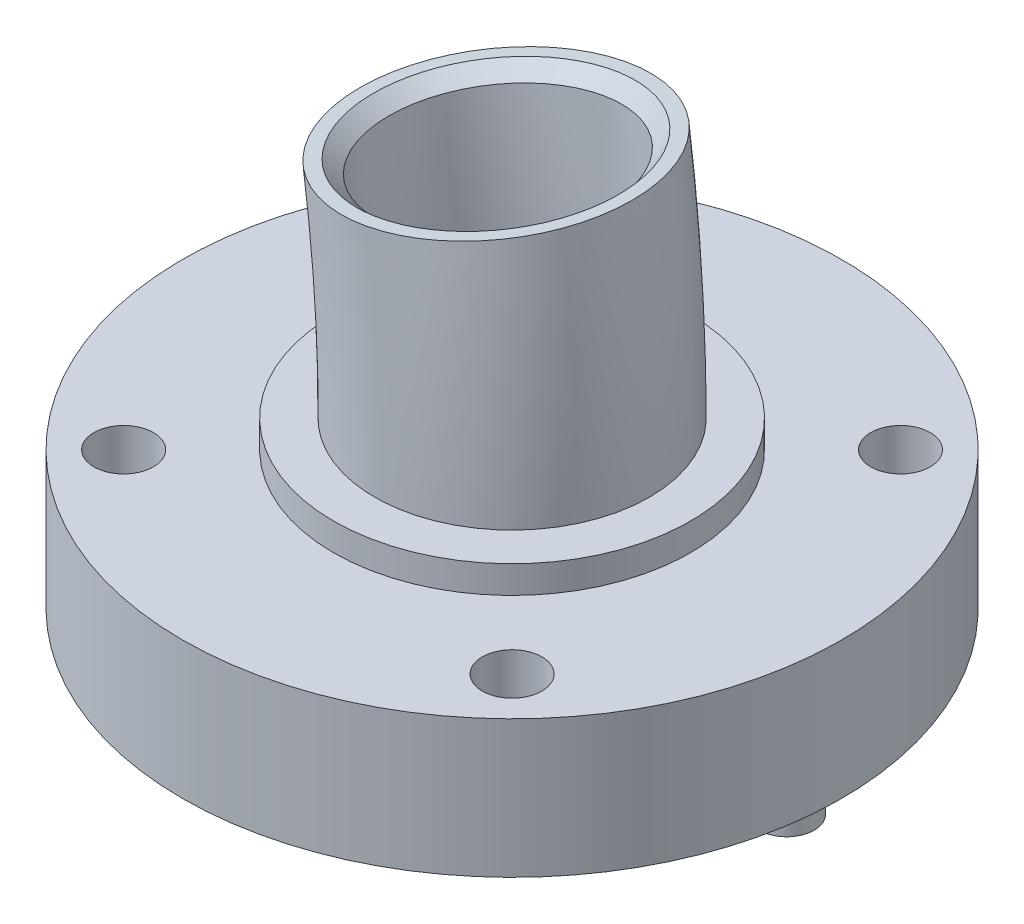
SolidWorks part; units mm, degrees
material "PMMA"
ref_plane "Front Plane" through (0, 0, 0) normal (0, 0, 1) x (1, 0, 0)
ref_plane "Top Plane" through (0, 0, 0) normal (0, 1, 0) x (1, 0, 0)
ref_plane "Right Plane" through (0, 0, 0) normal (1, 0, 0) x (0, 0, -1)
sketch "Sketch1" plane through (0, 0, 0) normal (0, 1, 0) x (1, 0, 0)
  circle A0 centre (0, 0) radius 30.48
  dimension "D1" = 60.96
extrude "Main Body Extrude" add sketch "Sketch1" along normal blind 12.7
sketch "Sketch32" plane through (0, 0, 0) normal (0, -1, 0) x (1, 0, 0)
  circle A0 centre (0, 0) radius 17
  dimension "D1" = 34
extrude "MHV Postioning Area" cut sketch "Sketch32" against normal blind 0.75 contours A0
sketch "Sketch43" plane through (0, 0.75, 0) normal (0, -1, 0) x (1, 0, 0)
  circle A0 centre (0, 0) radius 14.478
  dimension "D1" = 28.956
extrude "MHV Clearance Hole" cut sketch "Sketch43" against normal up to surface (11.95 mm away) up to face at (0, 12.7, 30.48)
sketch "Sketch18" plane through (0, 0, 0) normal (0, -1, 0) x (-1, 0, 0)
  line L0 (0, 0) -> (-25.4, 0) construction
  circle A0 centre (-25.4, 0) radius 2.54
  dimension "D1" = 5.08
  dimension "D2" = 25.4
extrude "Alignment Dowel" add sketch "Sketch18" along normal blind 3.81
pattern_circular "Dowel Pattern" count 2 over 360 about axis through (0, 0, 0) along (0, 1, 0) of "Alignment Dowel"
sketch "Sketch27" plane through (0, 0, 0) normal (0, -1, 0) x (1, 0, 0)
  line L0 (0, 0) -> (0, 25.4) construction
  circle A1 centre (0, 25.4) radius 2.5908
  dimension "D2" = 25.4
  dimension "D1" = 5.1816
extrude "Dowel Hole" cut sketch "Sketch27" against normal blind 3.81
pattern_circular "Dowel Hole Pattern" count 2 over 360 about axis through (0, 0, 0) along (0, 1, 0) of "Dowel Hole"
sketch "Sketch40" plane through (0, 0, 0) normal (0, -1, 0) x (-1, 0, 0)
  line L0 (0, 0) -> (17.9605, -17.9605) construction
  line L2 (0, 0) -> (30.48, 0) construction
  circle A0 centre (0, 0) radius 30.48 construction
  point P0 (17.9605, -17.9605)
  dimension "D2" = 45
hole_wizard "M5 Clearance Hole" positions "Sketch40" profile "Sketch39" hole size "M5" standard "ANSI Metric" end condition through all
sketch "Sketch39" plane through (-17.9605, 0, 17.9605) normal (1, 0, 0) x (0, 0, -1)
  line L0 (0, 0) -> (0, 12.7)
  line L1 (0, 12.7) -> (2.75, 12.7)
  line L2 (2.75, 12.7) -> (2.75, 0)
  line L5 (2.75, 0) -> (0, 0)
  line L11 (0, -6.35) -> (0, 107.95) construction
  dimension "Thru Hole Dia." = 5.5
  dimension "Thru Hole Depth" = 12.7
pattern_circular "Screw Hole Pattern" count 4 over 360 about axis through (0, 0, 0) along (0, 1, 0) of "M5 Clearance Hole"
sketch "Sketch54" plane through (0, 0, 0) normal (0, 0, 1) x (1, 0, 0)
  line L0 (-30.48, 0) -> (30.48, 0) construction
  line L1 (17.9832, 0) -> (20.6248, 0)
  line L2 (17.9832, 0) -> (17.9832, 1.2446)
  line L3 (17.9832, 1.2446) -> (20.6248, 1.2446)
  line L4 (20.6248, 0) -> (20.6248, 1.2446)
  line L5 (0, 0) -> (0, 6.4325) construction
  point P6 (20.6248, 0.6223)
  dimension "D1" = 2.6416
  dimension "D2" = 1.2446
  dimension "D3" = 20.6248
revolve "Cut-Revolve1" [suppressed] cut sketch "Sketch54" angle 360 about L5
sketch "Sketch55" plane through (0, 12.7, 0) normal (0, 1, 0) x (1, 0, 0)
  circle A2 centre (0, 0) radius 16.51
  dimension "D1" = 33.02
extrude "Boss-Extrude1" add sketch "Sketch55" along normal blind 2.54 separate body
sketch "Sketch57" plane through (0, 15.24, 0) normal (0, 1, 0) x (1, 0, 0)
  circle A0 centre (0, 0) radius 10.16
  dimension "D1" = 20.32
extrude "Cut-Extrude1" cut sketch "Sketch57" against normal through all and the other way through all
sketch "Sketch56" plane through (0, 15.24, 0) normal (0, 1, 0) x (1, 0, 0)
  line L0 (-152.4, 0) -> (-152.4, -40.8663) construction
  circle A0 centre (0, 0) radius 10.16
  circle A1 centre (0, 0) radius 12.7
  dimension "D1" = 25.4
  dimension "D2" = 20.32
  dimension "D3" = 152.4
revolve "Revolve1" add sketch "Sketch56" angle 8 about L0
sketch "Sketch58" plane through (0, 15.24, 0) normal (0, 1, 0) x (1, 0, 0)
  line L0 (0, -152.4) -> (98.4167, -152.4) construction
  circle A0 centre (0, 0) radius 12.7
  circle A1 centre (0, 0) radius 10.16 construction
  circle A2 centre (0, 0) radius 10.16
  dimension "D1" = 25.4
  dimension "D2" = 152.4
revolve "Revolve2" [suppressed] add sketch "Sketch58" angle 8 about L0
combine bodies "Combine2" operation type add bodies to combine 157 172
chamfer "Chamfer3" [suppressed] distance 1.27 angle 45
chamfer "Chamfer5" distance 1.27 angle 45 1 edges at (-1.4831, 36.45, 10.16)
equation "\"Dowel Distance\"= 1"
equation "\"D2@Sketch18\"=\"Dowel Distance\""
equation "\"D2@Sketch27\"=\"Dowel Distance\""
equation "\"Hole Distance\"= 1"
equation "\"D1@Sketch40\"=\"Hole Distance\""
equation "\"Body OD\"= 2.40in"
equation "\"Blood Fill Hole\"= 1.14in"
equation "\"D1@Sketch1\"=\"Body OD\""
